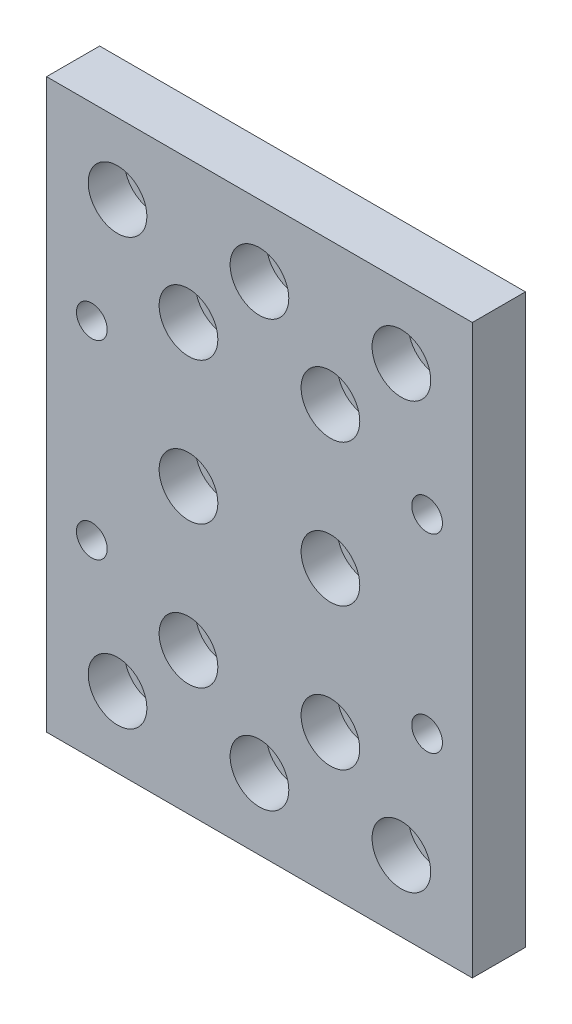
SolidWorks part; units mm, degrees
ref_plane "Front Plane" through (0, 0, 0) normal (0, 0, 1) x (1, 0, 0)
ref_plane "Top Plane" through (0, 0, 0) normal (0, 1, 0) x (1, 0, 0)
ref_plane "Right Plane" through (0, 0, 0) normal (1, 0, 0) x (0, 0, -1)
sketch "Sketch1" plane through (0, 0, 0) normal (0, 0, 1) x (1, 0, 0)
  line L0 (3.58, 49.6458) -> (3.58, 10.1458) construction
  line L1 (-59.17, 12.8958) -> (6.33, 12.8958) construction
  line L2 (-56.42, 44.1458) -> (-56.42, 15.6458) construction
  line L3 (-53.67, 46.8958) -> (0.83, 46.8958) construction
  line L4 (-64.52, 29.8958) -> (11.68, 29.8958) construction
  line L5 (-64.52, -20.9042) -> (11.68, -20.9042)
  line L6 (11.68, -20.9042) -> (11.68, 80.6958)
  line L7 (11.68, 80.6958) -> (-64.52, 80.6958)
  line L8 (-64.52, 80.6958) -> (-64.52, -20.9042)
  line L9 (-64.52, -20.9042) -> (11.68, -20.9042)
  line L10 (11.68, -20.9042) -> (11.68, 80.6958)
  line L11 (11.68, 80.6958) -> (-64.52, 80.6958)
  line L12 (-64.52, 80.6958) -> (-64.52, -20.9042)
  circle A0 centre (-1.02, 17.1958) radius 3.175 construction
  circle A1 centre (-13.72, 29.8958) radius 3.175
  circle A3 centre (-1.02, 42.5958) radius 3.175 construction
  circle A5 centre (-13.72, 55.2958) radius 3.175
  circle A7 centre (-1.02, 67.9958) radius 3.175
  circle A9 centre (-1.02, 17.1958) radius 3.429
  circle A10 centre (-1.02, 17.1958) radius 3.429 construction
  circle A11 centre (-13.72, 29.8958) radius 3.429
  circle A12 centre (-13.72, 29.8958) radius 3.429 construction
  circle A13 centre (-1.02, 42.5958) radius 3.429
  circle A14 centre (-1.02, 42.5958) radius 3.429 construction
  circle A15 centre (-13.72, 55.2958) radius 3.429
  circle A16 centre (-13.72, 55.2958) radius 3.429 construction
  circle A17 centre (-1.02, 67.9958) radius 3.429
  circle A18 centre (-1.02, 67.9958) radius 3.429 construction
  circle A19 centre (-26.42, 67.9958) radius 3.429
  circle A20 centre (-26.42, 67.9958) radius 3.429 construction
  circle A21 centre (-39.12, 55.2958) radius 3.429
  circle A22 centre (-39.12, 55.2958) radius 3.429 construction
  circle A23 centre (-51.82, 67.9958) radius 3.429
  circle A24 centre (-51.82, 67.9958) radius 3.429 construction
  circle A25 centre (-51.82, 42.5958) radius 3.429
  circle A26 centre (-51.82, 42.5958) radius 3.429 construction
  circle A27 centre (-51.82, 17.1958) radius 3.429
  circle A28 centre (-51.82, 17.1958) radius 3.429 construction
  circle A29 centre (-39.12, 29.8958) radius 3.429
  circle A30 centre (-39.12, 29.8958) radius 3.429 construction
  circle A31 centre (-39.12, 4.4958) radius 3.429
  circle A32 centre (-39.12, 4.4958) radius 3.429
  circle A33 centre (-13.72, 4.4958) radius 3.429
  circle A34 centre (-13.72, 4.4958) radius 3.429
  circle A35 centre (-1.02, -8.2042) radius 3.429
  circle A36 centre (-1.02, -8.2042) radius 3.429 construction
  circle A37 centre (-26.42, -8.2042) radius 3.429
  circle A38 centre (-26.42, -8.2042) radius 3.429 construction
  circle A39 centre (-51.82, -8.2042) radius 3.429
  circle A40 centre (-51.82, -8.2042) radius 3.429 construction
  circle A41 centre (-26.42, 67.9958) radius 3.175
  circle A42 centre (-39.12, 55.2958) radius 3.175
  circle A43 centre (-51.82, 67.9958) radius 3.175
  circle A44 centre (-51.82, 42.5958) radius 3.175 construction
  circle A45 centre (-51.82, 17.1958) radius 3.175 construction
  circle A46 centre (-39.12, 29.8958) radius 3.175
  circle A47 centre (-39.12, 4.4958) radius 3.229 construction
  circle A48 centre (-13.72, 4.4958) radius 3.229 construction
  circle A49 centre (-1.02, -8.2042) radius 3.175
  circle A50 centre (-26.42, -8.2042) radius 3.175
  circle A51 centre (-51.82, -8.2042) radius 3.175
  circle A60 centre (-56.42, 46.8958) radius 2.75
  circle A61 centre (3.58, 46.8958) radius 2.75
  circle A62 centre (-56.42, 12.8958) radius 2.75
  circle A63 centre (3.58, 12.8958) radius 2.75
  point P84 (3.58, 29.8958)
  point P85 (11.68, 29.8958)
  point P86 (-26.42, 46.8958)
  point P87 (-26.42, 80.6958)
  dimension "D3" = 6.35
  dimension "D21" = 65.5
  dimension "D22" = 39.5
  dimension "D23" = 28.5
  dimension "D4" = 0
  dimension "D5" = 0
  dimension "D6" = 0
  dimension "D7" = 0
  dimension "D8" = 0
  dimension "D9" = 0
  dimension "D10" = 0
  dimension "D11" = 0
  dimension "D12" = 0
  dimension "D13" = 0
  dimension "D14" = 0
  dimension "D15" = 0
  dimension "D16" = 0
  dimension "D17" = 0
  dimension "D18" = 0
  dimension "D19" = 0
  dimension "D20" = 0
extrude "Boss-Extrude1" add sketch "Sketch1" along normal blind 9.5
sketch "草图1" plane through (0, 0, 9.5) normal (0, 0, 1) x (1, 0, 0)
  line L0 (-64.52, 29.8958) -> (11.68, 29.8958) construction
  line L1 (-64.52, 80.6958) -> (-64.52, -20.9042) construction
  line L2 (11.68, -20.9042) -> (11.68, 80.6958) construction
  circle A0 centre (-51.82, -8.2042) radius 3.175 construction
  circle A1 centre (-26.42, -8.2042) radius 3.175 construction
  circle A2 centre (-1.02, -8.2042) radius 3.175 construction
  circle A5 centre (-39.12, 29.8958) radius 3.175 construction
  circle A6 centre (-13.72, 29.8958) radius 3.175 construction
  circle A9 centre (-39.12, 55.2958) radius 3.175 construction
  circle A10 centre (-13.72, 55.2958) radius 3.175 construction
  circle A11 centre (-1.02, 67.9958) radius 3.175 construction
  circle A12 centre (-26.42, 67.9958) radius 3.175 construction
  circle A13 centre (-51.82, 67.9958) radius 3.175 construction
  circle A14 centre (-51.82, -8.2042) radius 3.175 construction
  circle A15 centre (-26.42, -8.2042) radius 3.175 construction
  circle A16 centre (-1.02, -8.2042) radius 3.175 construction
  circle A19 centre (-39.12, 29.8958) radius 3.175 construction
  circle A20 centre (-13.72, 29.8958) radius 3.175 construction
  circle A23 centre (-39.12, 55.2958) radius 3.175 construction
  circle A24 centre (-13.72, 55.2958) radius 3.175 construction
  circle A25 centre (-1.02, 67.9958) radius 3.175 construction
  circle A26 centre (-26.42, 67.9958) radius 3.175 construction
  circle A27 centre (-51.82, 67.9958) radius 3.175 construction
  circle A28 centre (-51.82, -8.2042) radius 5.25
  circle A29 centre (-26.42, -8.2042) radius 5.25
  circle A30 centre (-1.02, -8.2042) radius 5.25
  circle A33 centre (-39.12, 29.8958) radius 5.25
  circle A34 centre (-13.72, 29.8958) radius 5.25
  circle A37 centre (-39.12, 55.2958) radius 5.25
  circle A38 centre (-13.72, 55.2958) radius 5.25
  circle A39 centre (-1.02, 67.9958) radius 5.25
  circle A40 centre (-26.42, 67.9958) radius 5.25
  circle A41 centre (-51.82, 67.9958) radius 5.25
  circle A42 centre (-13.72, 4.4958) radius 3.175 construction
  circle A43 centre (-39.12, 4.4958) radius 3.175 construction
  circle A44 centre (-13.72, 4.4958) radius 5.25
  circle A45 centre (-39.12, 4.4958) radius 5.25
  dimension "D1" = 10.5
extrude "切除-拉伸1" cut sketch "草图1" against normal blind 6.5
